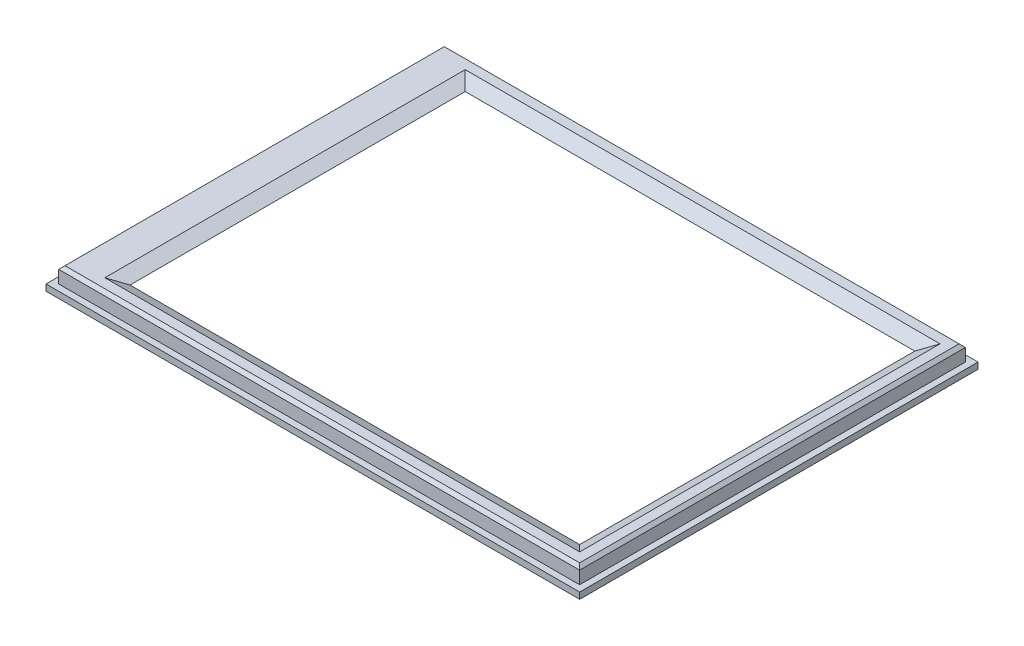
SolidWorks part; units mm, degrees
ref_plane "Front Plane" through (0, 0, 0) normal (0, 0, 1) x (1, 0, 0)
ref_plane "Top Plane" through (0, 0, 0) normal (0, 1, 0) x (1, 0, 0)
ref_plane "Right Plane" through (0, 0, 0) normal (1, 0, 0) x (0, 0, -1)
sketch "Sketch1" plane through (0, 0, 0) normal (0, 1, 0) x (1, 0, 0)
  line L0 (2, 2) -> (82.4, 2)
  line L1 (0, 0) -> (84.4, 0)
  line L2 (0, 0) -> (0, 63)
  line L3 (0, 63) -> (84.4, 63)
  line L4 (84.4, 0) -> (84.4, 63)
  line L5 (82.4, 2) -> (82.4, 61)
  line L6 (2, 61) -> (82.4, 61)
  line L7 (2, 2) -> (2, 61)
  dimension "D1" = 84.4
  dimension "D2" = 63
  dimension "D3" = 2
extrude "Boss-Extrude1" add sketch "Sketch1" along normal blind 1
sketch "Sketch2" plane through (0, 1, 0) normal (0, 1, 0) x (1, 0, 0)
  line L0 (1, 62) -> (83.4, 62)
  line L1 (2, 61) -> (82.4, 61)
  line L2 (2, 61) -> (2, 2)
  line L3 (2, 2) -> (82.4, 2)
  line L4 (82.4, 61) -> (82.4, 2)
  line L5 (83.4, 62) -> (83.4, 1)
  line L6 (1, 1) -> (83.4, 1)
  line L7 (1, 62) -> (1, 1)
  dimension "D1" = 1
extrude "Boss-Extrude2" add sketch "Sketch2" along normal blind 2.5
sketch "Sketch3" plane through (0, 3.5, 0) normal (0, 1, 0) x (1, 0, 0)
  line L0 (2, 61) -> (2, 2) construction
  line L1 (1, 62) -> (83.4, 62)
  line L2 (1, 62) -> (1, 1)
  line L3 (1, 1) -> (83.4, 1)
  line L4 (83.4, 62) -> (83.4, 1)
  line L5 (8.3, 58) -> (79.4, 58)
  line L6 (8.3, 58) -> (8.3, 5)
  line L7 (8.3, 5) -> (79.4, 5)
  line L8 (79.4, 58) -> (79.4, 5)
  line L9 (82.4, 61) -> (2, 61) construction
  dimension "D1" = 6.3
  dimension "D2" = 3
  dimension "D3" = 71.1
  dimension "D4" = 53
extrude "Boss-Extrude3" add sketch "Sketch3" against normal blind 1
chamfer "Chamfer1" distance 2 distance2 1 4 edges at (79.4, 3.5, -31.5) (43.85, 3.5, -5) (8.3, 3.5, -31.5) (43.85, 3.5, -58) first distance on face at (42.2, 3.5, -31.5)
chamfer "Chamfer2" distance 0.5 angle 45 4 edges at (42.2, 3.5, -1) (83.4, 3.5, -31.5) (42.2, 3.5, -62) (1, 3.5, -31.5)
